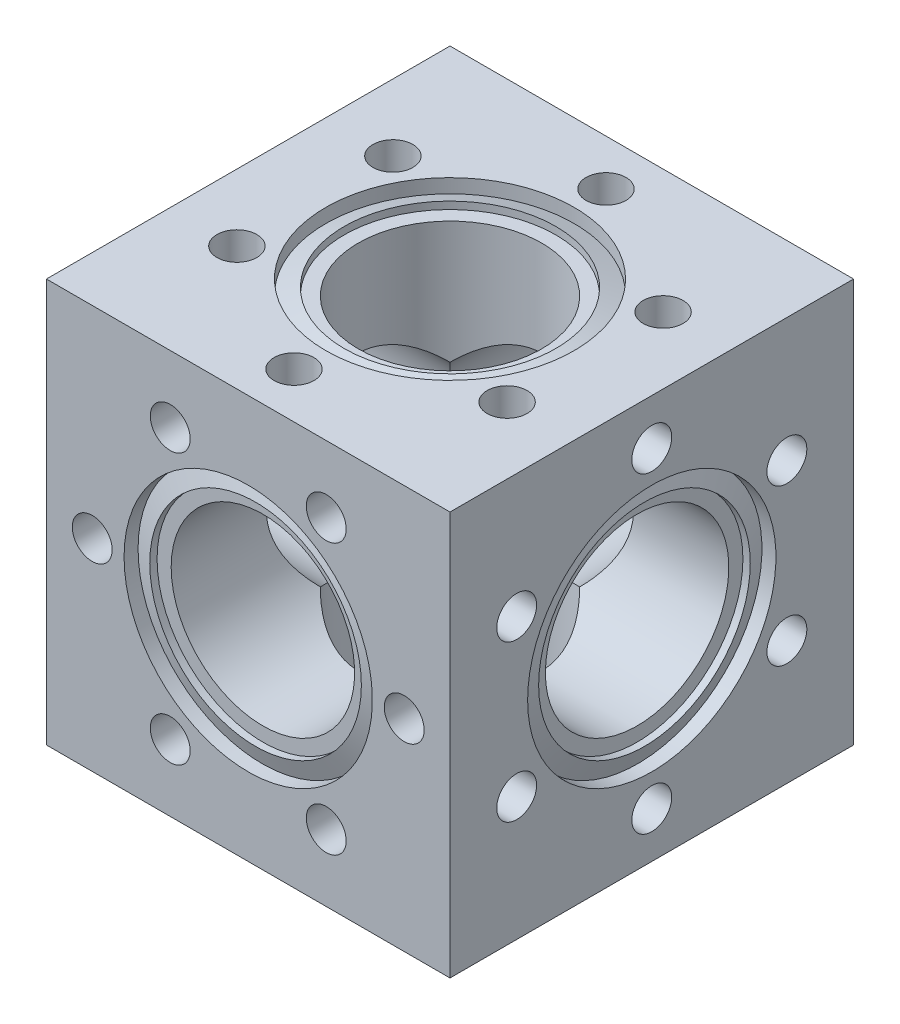
SolidWorks part; units mm, degrees
material "AISI 304"
ref_plane "Front Plane" through (0, 0, 0) normal (0, 0, 1) x (1, 0, 0)
ref_plane "Top Plane" through (0, 0, 0) normal (0, 1, 0) x (1, 0, 0)
ref_plane "Right Plane" through (0, 0, 0) normal (1, 0, 0) x (0, 0, -1)
sketch "Sketch1" plane through (0, 0, 0) normal (0, 0, 1) x (1, 0, 0)
  line L1 (17.4625, -17.4625) -> (-17.4625, -17.4625)
  line L2 (17.4625, -17.4625) -> (17.4625, 17.4625)
  line L3 (17.4625, 17.4625) -> (-17.4625, 17.4625)
  line L4 (-17.4625, -17.4625) -> (-17.4625, 17.4625)
  line L5 (17.4625, -17.4625) -> (-17.4625, 17.4625) construction
  line L6 (17.4625, 17.4625) -> (-17.4625, -17.4625) construction
  point P0 (0, 0)
  dimension "D1" = 17.4625
extrude "Boss-Extrude1" add sketch "Sketch1" along normal mid plane 34.925
ref_axis "Axis1" through (-38.4175, 0, 0) along (1, 0, 0)
ref_axis "Axis2" through (0, 38.4175, 0) along (0, -1, 0)
ref_axis "Axis3" through (0, 0, 38.4175) along (0, 0, -1)
sketch "Sketch6" plane through (0, 0, 0) normal (0, 0, 1) x (1, 0, 0)
  line L0 (17.4625, 10.7442) -> (16.2497, 10.7442)
  line L1 (17.4625, -17.4625) -> (17.4625, 17.4625) construction
  line L2 (16.2497, 10.7442) -> (16.8275, 9.1567)
  line L3 (16.8275, 9.1567) -> (16.1925, 9.1567)
  line L4 (16.1925, 9.1567) -> (16.1925, 7.9375)
  line L5 (-38.4175, 0) -> (38.4175, 0) construction
  line L6 (0, 0) -> (17.4625, 0)
  line L7 (17.4625, 0) -> (17.4625, 10.7442)
  line L8 (17.4625, 0) -> (68.0068, 0) construction
  line L9 (16.1925, 7.9375) -> (0, 7.9375)
  line L10 (0, 38.4175) -> (0, -38.4175) construction
  line L11 (0, 7.9375) -> (0, 0)
  dimension "D1" = 20
  dimension "D2" = 1.5875
  dimension "D3" = 0.635
  dimension "D4" = 1.27
  dimension "D5" = 21.4884
  dimension "D6" = 15.875
revolve "Cut-Revolve1" cut sketch "Sketch6" angle 360 about L8
hole_wizard " Tapped Hole0" positions "Sketch4" profile "Sketch5" tap size "#8-32" standard "ANSI Inch"
sketch "Sketch4" plane through (17.4625, 0, 0) normal (1, 0, 0) x (0, 0, -1)
  circle A0 centre (0, 0) radius 13.5001 construction
  point P0 (0, 13.5001)
  dimension "D1" = 27.0002
sketch "Sketch5" plane through (17.4625, 13.5001, 0) normal (0, 1, 0) x (0, 0, -1)
  line L0 (0, 0) -> (0, 7.3878)
  line L1 (0, 7.3878) -> (1.7272, 6.35)
  line L2 (1.7272, 6.35) -> (1.7272, 0)
  line L5 (1.7272, 0) -> (0, 0)
  line L10 (0, 7.3878) -> (-1.7272, 6.35) construction
  line L11 (0, -6.35) -> (0, 107.95) construction
  dimension "Tap Drill Dia." = 3.4544
  dimension "Tap Drill Depth" = 6.35
  dimension "Drill Angle" = 118
cosmetic thread "Hole Thread1" parameters "D1"=8.3312, "D2"=4.1656
hole_wizard " Tapped Hole1" positions "Sketch9" profile "Sketch8" tap size "#8-32" standard "ANSI Inch"
sketch "Sketch9" plane through (0, 17.4625, 0) normal (0, 1, 0) x (1, 0, 0)
  circle A0 centre (0, 0) radius 13.5001 construction
  point P0 (0, 13.5001)
  dimension "D1" = 27.0002
sketch "Sketch8" plane through (0, 17.4625, -13.5001) normal (1, 0, 0) x (0, 0, 1)
  line L0 (0, 0) -> (0, 7.3878)
  line L1 (0, 7.3878) -> (1.7272, 6.35)
  line L2 (1.7272, 6.35) -> (1.7272, 0)
  line L5 (1.7272, 0) -> (0, 0)
  line L10 (0, 7.3878) -> (-1.7272, 6.35) construction
  line L11 (0, -6.35) -> (0, 107.95) construction
  dimension "Tap Drill Dia." = 3.4544
  dimension "Tap Drill Depth" = 6.35
  dimension "Drill Angle" = 118
cosmetic thread "Hole Thread2" parameters "D1"=8.3312, "D2"=4.1656
hole_wizard " Tapped Hole2" positions "Sketch11" profile "Sketch10" tap size "#8-32" standard "ANSI Inch"
sketch "Sketch11" plane through (0, 0, 17.4625) normal (0, 0, 1) x (1, 0, 0)
  circle A0 centre (0, 0) radius 13.5001 construction
  point P0 (13.5001, 0)
  dimension "D1" = 27.0002
sketch "Sketch10" plane through (13.5001, 0, 17.4625) normal (1, 0, 0) x (0, -1, 0)
  line L0 (0, 0) -> (0, 7.3878)
  line L1 (0, 7.3878) -> (1.7272, 6.35)
  line L2 (1.7272, 6.35) -> (1.7272, 0)
  line L5 (1.7272, 0) -> (0, 0)
  line L10 (0, 7.3878) -> (-1.7272, 6.35) construction
  line L11 (0, -6.35) -> (0, 107.95) construction
  dimension "Tap Drill Dia." = 3.4544
  dimension "Tap Drill Depth" = 6.35
  dimension "Drill Angle" = 118
cosmetic thread "Hole Thread3" parameters "D1"=8.3312, "D2"=4.1656
pattern_circular "CirPattern1" count 6 over 360 about axis through (-38.4175, 0, 0) along (1, 0, 0) of " Tapped Hole0"
pattern_circular "CirPattern2" count 6 over 360 about axis through (0, 38.4175, 0) along (0, -1, 0) of " Tapped Hole1"
pattern_circular "CirPattern3" count 6 over 360 about axis through (0, 0, 38.4175) along (0, 0, -1) of " Tapped Hole2"
pattern_circular "CirPattern4" count 4 over 360 about axis through (0, 38.4175, 0) along (0, -1, 0) of "Cut-Revolve1"
pattern_circular "CirPattern5" count 4 over 360 about axis through (0, 0, 38.4175) along (0, 0, -1) skipping 2 of "Cut-Revolve1"
mirror "Mirror1" about plane through (0, 0, 0) normal (0, 0, 1) of "CirPattern3"
mirror "Mirror2" about plane through (0, 0, 0) normal (0, 1, 0) of "CirPattern2"
mirror "Mirror3" about plane through (0, 0, 0) normal (1, 0, 0) of "CirPattern1"
equation "\"D1@Boss-Extrude1\"=\"D1@Sketch1\"*2"
equation "\"D1@Sketch9\"=\"D1@Sketch4\""
equation "\"D1@Sketch11\"=\"D1@Sketch4\""
